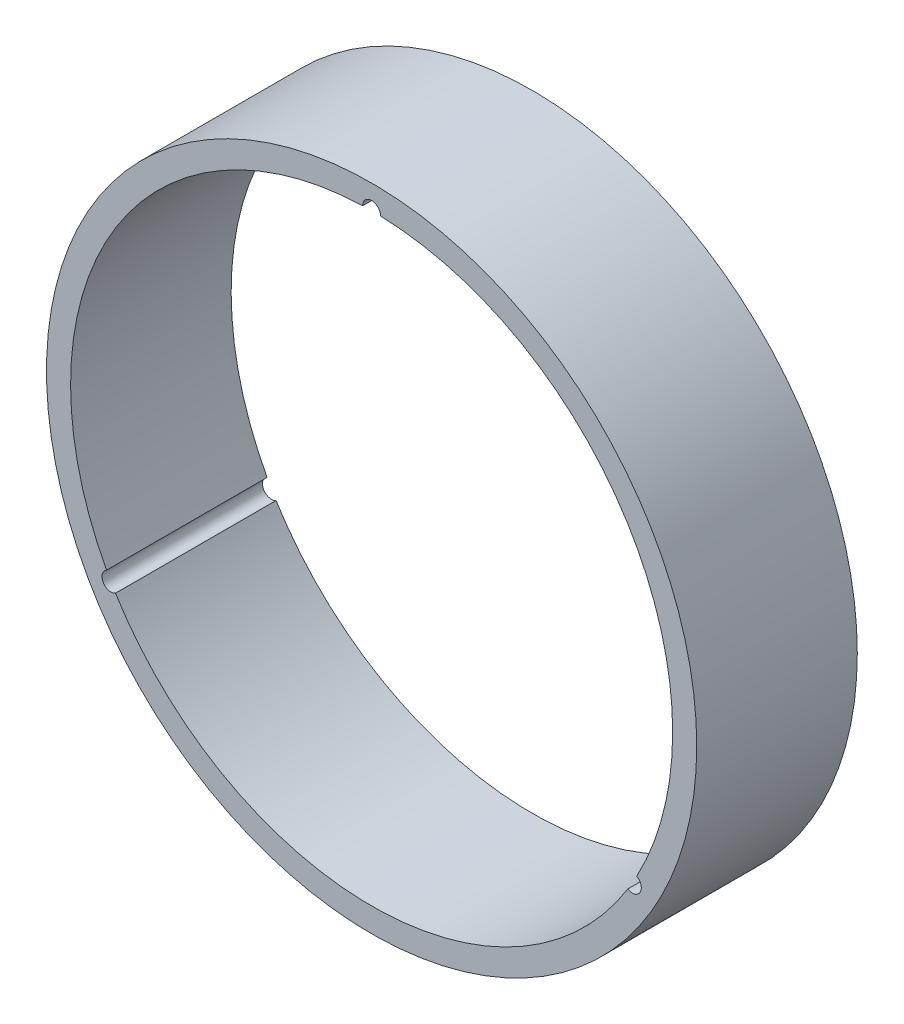
SolidWorks part; units mm, degrees
material "ABS"
ref_plane "Front Plane" through (0, 0, 0) normal (0, 0, 1) x (1, 0, 0)
ref_plane "Top Plane" through (0, 0, 0) normal (0, 1, 0) x (1, 0, 0)
ref_plane "Right Plane" through (0, 0, 0) normal (1, 0, 0) x (0, 0, -1)
sketch "Sketch1" plane through (0, 0, 0) normal (0, 0, 1) x (1, 0, 0)
  line L0 (0, 75) -> (0, 0) construction
  line L1 (0, 0) -> (75, 0) construction
  circle A0 centre (0, 0) radius 75
  circle A1 centre (0, 0) radius 81
  circle A2 centre (0, 75) radius 2.2319
  circle A3 centre (64.9519, -37.5) radius 2.2319
  circle A4 centre (-64.9519, -37.5) radius 2.2319
  point P13 (0, 0)
  dimension "D1" = 150
  dimension "D2" = 6
  dimension "D3" = 90
  dimension "D4" = 3
extrude "Boss-Extrude1" add sketch "Sketch1" along normal mid plane 40 contours A1 A4 A0 A2 A3 region at (-78.709, 0, 0)
